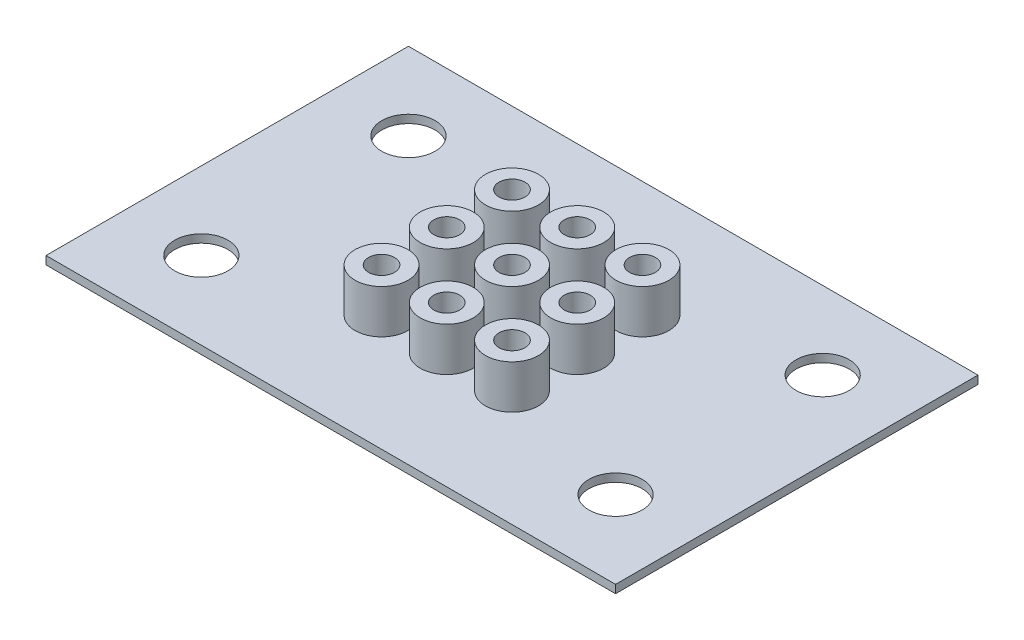
SolidWorks part; units mm, degrees
ref_plane "Front Plane" through (0, 0, 0) normal (0, 0, 1) x (1, 0, 0)
ref_plane "Top Plane" through (0, 0, 0) normal (0, 1, 0) x (1, 0, 0)
ref_plane "Right Plane" through (0, 0, 0) normal (1, 0, 0) x (0, 0, -1)
sketch "Sketch1" plane through (0, 0, 0) normal (0, 1, 0) x (1, 0, 0)
  line L0 (9.525, 34.925) -> (0, 34.925) construction
  line L1 (0, 0) -> (69.85, 0)
  line L2 (0, 0) -> (0, 44.45)
  line L3 (0, 44.45) -> (69.85, 44.45)
  line L4 (69.85, 0) -> (69.85, 44.45)
  line L5 (9.525, 34.925) -> (60.325, 34.925) construction
  line L6 (9.525, 34.925) -> (9.525, 9.525) construction
  line L7 (9.525, 9.525) -> (60.325, 9.525) construction
  line L8 (60.325, 34.925) -> (60.325, 9.525) construction
  line L9 (9.525, 34.925) -> (9.525, 44.45) construction
  line L10 (34.925, 22.225) -> (34.925, 30.225) construction
  circle A0 centre (9.525, 34.925) radius 3.2639
  circle A1 centre (60.325, 34.925) radius 3.2639
  circle A2 centre (9.525, 9.525) radius 3.2639
  circle A3 centre (60.325, 9.525) radius 3.2639
  circle A4 centre (34.925, 22.225) radius 1.25
  circle A5 centre (42.925, 22.225) radius 1.25
  circle A6 centre (42.925, 30.225) radius 1.25
  circle A7 centre (34.925, 30.225) radius 1.25
  circle A8 centre (26.925, 22.225) radius 1.25
  circle A9 centre (26.925, 30.225) radius 1.25
  circle A10 centre (34.925, 30.225) radius 1.25
  circle A11 centre (42.925, 22.225) radius 1.25
  circle A12 centre (42.925, 14.225) radius 1.25
  circle A13 centre (34.925, 14.225) radius 1.25
  circle A14 centre (26.925, 22.225) radius 1.25
  circle A15 centre (26.925, 14.225) radius 1.25
  circle A16 centre (34.925, 14.225) radius 1.25
  point P13 (34.925, 34.925)
  point P14 (34.925, 44.45)
  point P20 (69.85, 22.225)
  dimension "D5" = 6.5278
  dimension "D6" = 2.5
  dimension "D1" = 69.85
  dimension "D2" = 44.45
  dimension "D3" = 50.8
  dimension "D4" = 25.4
  dimension "D9" = 8
  dimension "D7" = 2
  dimension "D8" = 2
  dimension "D10" = 2
  dimension "D11" = 2
  dimension "D12" = 2
  dimension "D13" = 2
  dimension "D14" = 2
  dimension "D15" = 2
extrude "Boss-Extrude1" add sketch "Sketch1" along normal blind 1 contours L1 L4 L3 L2 A15 A13 A12 A9 A8 A7 A6 A5 A4 A3 A2 A1 A0 region at (0.8279, 0, -22.225)
sketch "Sketch2" plane through (0, 1, 0) normal (0, 1, 0) x (1, 0, 0)
  line L0 (34.925, 22.225) -> (34.925, 30.225) construction
  circle A0 centre (34.925, 22.225) radius 3.25
  circle A1 centre (34.925, 22.225) radius 1.59
  circle A2 centre (42.925, 22.225) radius 3.25
  circle A3 centre (42.925, 22.225) radius 1.59
  circle A4 centre (42.925, 30.225) radius 3.25
  circle A5 centre (42.925, 30.225) radius 1.59
  circle A6 centre (34.925, 30.225) radius 3.25
  circle A7 centre (34.925, 30.225) radius 1.59
  circle A8 centre (42.925, 22.225) radius 1.59
  circle A9 centre (42.925, 22.225) radius 3.25
  circle A10 centre (42.925, 14.225) radius 1.59
  circle A11 centre (42.925, 14.225) radius 3.25
  circle A12 centre (34.925, 14.225) radius 1.59
  circle A13 centre (34.925, 14.225) radius 3.25
  circle A14 centre (26.925, 22.225) radius 3.25
  circle A15 centre (26.925, 22.225) radius 1.59
  circle A16 centre (26.925, 30.225) radius 3.25
  circle A17 centre (26.925, 30.225) radius 1.59
  circle A18 centre (34.925, 30.225) radius 3.25
  circle A19 centre (34.925, 30.225) radius 1.59
  circle A20 centre (26.925, 22.225) radius 1.59
  circle A21 centre (26.925, 22.225) radius 3.25
  circle A22 centre (26.925, 14.225) radius 1.59
  circle A23 centre (26.925, 14.225) radius 3.25
  circle A24 centre (34.925, 14.225) radius 1.59
  circle A25 centre (34.925, 14.225) radius 3.25
  dimension "D1" = 3.18
  dimension "D2" = 6.5
  dimension "D5" = 8
  dimension "D3" = 2
  dimension "D4" = 2
  dimension "D6" = 2
  dimension "D7" = 2
  dimension "D8" = 2
  dimension "D9" = 2
extrude "Boss-Extrude2" add sketch "Sketch2" along normal blind 5.35 contours A16 A17 | A14 A15 | A6 A7 | A4 A5 | A2 A3 | A1 A0 | A23 A22 | A13 A12 | A11 A10 region at (31.7669, 1, -22.225) region at (39.7669, 1, -22.225) region at (39.7669, 1, -30.225) region at (31.7669, 1, -30.225) region at (39.7669, 1, -14.225) region at (31.7669, 1, -14.225) region at (23.7669, 1, -22.225) region at (23.7669, 1, -30.225) region at (23.7669, 1, -14.225)
